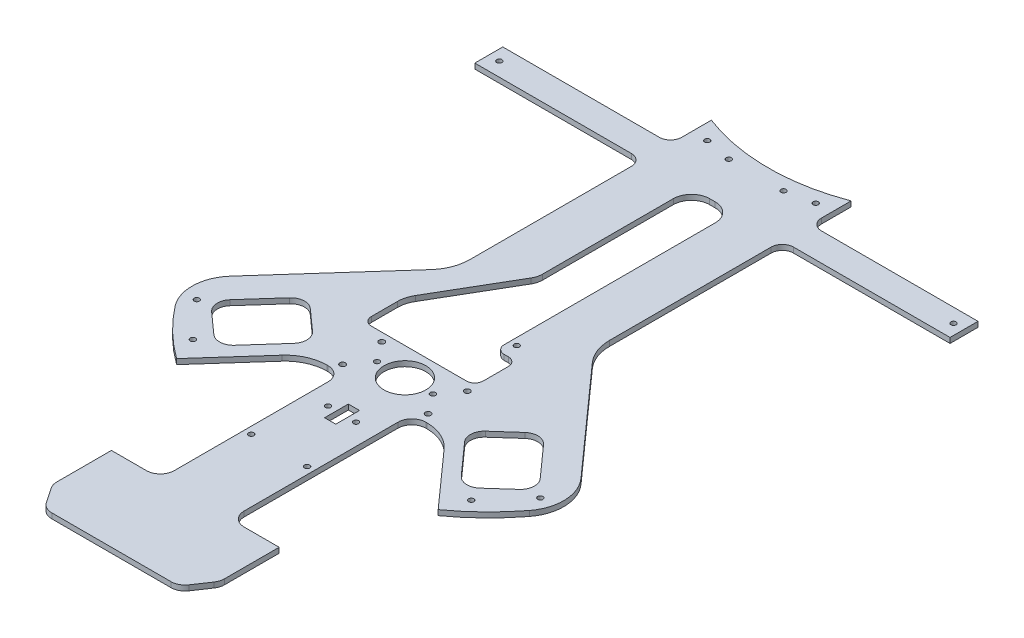
SolidWorks part; units mm, degrees
material "6063-T1"
ref_plane "Front Plane" through (0, 0, 0) normal (0, 0, 1) x (1, 0, 0)
ref_plane "Top Plane" through (0, 0, 0) normal (0, 1, 0) x (1, 0, 0)
ref_plane "Right Plane" through (0, 0, 0) normal (1, 0, 0) x (0, 0, -1)
sketch "Sketch1" plane through (0, 0, 0) normal (0, 1, 0) x (1, 0, 0)
  line L0 (-63.5, 31.75) -> (-178.5164, -97.0677)
  line L1 (-215.9, 31.75) -> (215.9, 31.75)
  line L2 (-215.9, 31.75) -> (-215.9, -31.75)
  line L3 (-215.9, -31.75) -> (215.9, -31.75)
  line L4 (215.9, 31.75) -> (215.9, -31.75)
  line L5 (-215.9, 31.75) -> (215.9, -31.75) construction
  line L6 (-215.9, -31.75) -> (215.9, 31.75) construction
  line L7 (63.5, 31.75) -> (-63.5, 31.75)
  line L8 (63.5, 31.75) -> (63.5, 292.608)
  line L9 (63.5, 292.608) -> (-63.5, 292.608)
  line L10 (-63.5, 31.75) -> (-63.5, 292.608)
  line L11 (0, -31.75) -> (-118.8264, -164.8348)
  line L12 (0, -31.75) -> (118.8264, -164.8348)
  line L13 (63.5, 31.75) -> (178.5164, -97.0677)
  line L14 (-62.3664, -101.6) -> (62.3664, -101.6)
  circle A1 centre (0, 0) radius 25.4 construction
  circle A2 centre (-25.4, 0) radius 2.3813
  circle A3 centre (25.4, 0) radius 2.3812
  circle A4 centre (0, 0) radius 203.2
  circle A5 centre (0, -76.2) radius 25.4 construction
  circle A6 centre (-25.4, -76.2) radius 2.3813
  circle A7 centre (25.4, -76.2) radius 2.3813
  point P0 (0, 0)
  dimension "D5" = 4.7625
  dimension "D6" = 4.7625
  dimension "D7" = 101.6
  dimension "D8" = 50.8
  dimension "D10" = 406.4
  dimension "D14" = 4.7625
  dimension "D15" = 4.7625
  dimension "D16" = 50.8
  dimension "D1" = 431.8
  dimension "D2" = 63.5
  dimension "D3" = 127
  dimension "D4" = 63.5
  dimension "D9" = 260.858
  dimension "D11" = 59.69
  dimension "D12" = 59.69
  dimension "D13" = 76.2
extrude "Boss-Extrude1" add sketch "Sketch1" along normal blind 4.7625 contours L10 L1 L8 L9 | L4 L1 L2 L3 A3 A2 | L0 A4 L11 L3 | L12 A4 L13 L3 | A4 L8 L9 L10 | L11 L14 L12 region at (0, 0, 3.2765) region at (0, 0, -115.8234) region at (-100.5416, 0, 84.5084) region at (0, 0, -246.176) region at (0, 0, 78.3341) region at (100.5416, 0, 84.5084)
sketch "Sketch2" plane through (0, 4.7625, 0) normal (0, 1, 0) x (1, 0, 0)
  line L0 (0, 292.608) -> (0, -101.6) construction
  line L1 (63.5, 292.608) -> (-63.5, 292.608) construction
  line L2 (-62.3664, -101.6) -> (62.3664, -101.6) construction
  circle A0 centre (25.4, 279.908) radius 2.3813
  circle A1 centre (50.8, 279.908) radius 2.3813
  circle A2 centre (-50.8, 279.908) radius 2.3813
  circle A3 centre (-25.4, 279.908) radius 2.3813
  dimension "D3" = 4.7625
  dimension "D4" = 4.7625
  dimension "D1" = 25.4
  dimension "D2" = 50.8
  dimension "D5" = 12.7
  dimension "D6" = 12.7
extrude "Cut-Extrude1" cut sketch "Sketch2" against normal through all
fillet "Fillet1" radius 38.1 4 edges at (63.5, 2.3813, -31.75) (-63.5, 2.3813, -31.75) (62.3664, 2.3813, 101.6) (-62.3664, 2.3813, 101.6)
sketch "Sketch4" plane through (0, 4.7625, 0) normal (0, 1, 0) x (1, 0, 0)
  line L0 (0, 292.608) -> (0, 0) construction
  line L1 (63.5, 292.608) -> (-63.5, 292.608) construction
  line L2 (0, 0) -> (0, -190.5) construction
  line L3 (0, 0) -> (-156.0485, -109.2663) construction
  circle A0 centre (0, 0) radius 190.5 construction
  circle A1 centre (-156.0485, -109.2663) radius 2.3813
  circle A2 centre (-126.4791, -142.4545) radius 2.3813
  circle A3 centre (126.4791, -142.4545) radius 2.3813
  circle A4 centre (156.0485, -109.2663) radius 2.3813
  dimension "D1" = 381
  dimension "D4" = 4.7625
  dimension "D5" = 4.7625
  dimension "D2" = 44.45
  dimension "D3" = 55
extrude "Cut-Extrude3" cut sketch "Sketch4" against normal through all
fillet "Fillet2" radius 38.1 2 edges at (178.5164, 2.3813, 97.0677) (-178.5164, 2.3813, 97.0677)
sketch "Sketch5" plane through (0, 4.7625, 0) normal (0, 1, 0) x (1, 0, 0)
  line L0 (-149.2765, -103.5959) -> (-111.3829, -137.4296)
  line L1 (-149.2765, -103.5959) -> (-106.9843, -56.229)
  line L2 (-111.3829, -137.4296) -> (-69.0908, -90.0627)
  line L3 (-106.9843, -56.229) -> (-69.0908, -90.0627)
  line L8 (-73.7278, -114.3247) -> (-118.8264, -164.8348) construction
  line L9 (0, 292.608) -> (0, -101.6) construction
  line L10 (63.5, 292.608) -> (-63.5, 292.608) construction
  line L11 (106.9843, -56.229) -> (69.0908, -90.0627)
  line L12 (111.3829, -137.4296) -> (69.0908, -90.0627)
  line L13 (149.2765, -103.5959) -> (106.9843, -56.229)
  line L14 (149.2765, -103.5959) -> (111.3829, -137.4296)
  line L15 (-45.3077, -101.6) -> (45.3077, -101.6) construction
  dimension "D1" = 50.8
  dimension "D2" = 12.7
  dimension "D3" = 63.5
  dimension "D4" = 25.4
extrude "Cut-Extrude4" cut sketch "Sketch5" against normal through all
fillet "Fillet3" radius 12.7 8 edges at (111.3829, 2.3813, 137.4296) (69.0908, 2.3813, 90.0627) (106.9843, 2.3813, 56.229) (149.2765, 2.3813, 103.5959) (-69.0908, 2.3813, 90.0627) (-106.9843, 2.3813, 56.229) (-149.2765, 2.3813, 103.5959) (-111.3829, 2.3813, 137.4296)
sketch "Sketch6" plane through (0, 4.7625, 0) normal (0, 1, 0) x (1, 0, 0)
  circle A0 centre (0, -76.2) radius 19.05
  dimension "D1" = 38.1
  dimension "D2" = 76.2
extrude "Cut-Extrude5" cut sketch "Sketch6" against normal through all
sketch "Sketch7" plane through (0, 4.7625, 0) normal (0, 1, 0) x (1, 0, 0)
  line L0 (-45.3077, -101.6) -> (45.3077, -101.6) construction
  line L1 (-19.05, 203.2) -> (19.05, 203.2)
  line L2 (-19.05, 203.2) -> (-19.05, -50.8)
  line L3 (-19.05, -50.8) -> (19.05, -50.8)
  line L4 (19.05, 203.2) -> (19.05, -50.8)
  line L5 (-19.05, 203.2) -> (19.05, -50.8) construction
  line L6 (-19.05, -50.8) -> (19.05, 203.2) construction
  point P0 (0, 76.2)
  dimension "D1" = 38.1
  dimension "D2" = 50.8
  dimension "D3" = 254
extrude "Cut-Extrude6" cut sketch "Sketch7" against normal through all
sketch "Sketch8" plane through (0, 4.7625, 0) normal (0, 1, 0) x (1, 0, 0)
  line L0 (-19.05, -50.8) -> (19.05, -50.8) construction
  line L1 (-63.5, -50.8) -> (38.1, -50.8)
  line L2 (-63.5, -50.8) -> (-63.5, -12.7)
  line L3 (-63.5, -12.7) -> (38.1, -12.7)
  line L4 (38.1, -50.8) -> (38.1, -12.7)
  dimension "D1" = 101.6
  dimension "D2" = 38.1
  dimension "D3" = 38.1
extrude "Cut-Extrude7" cut sketch "Sketch8" against normal through all
sketch "Sketch9" plane through (0, 4.7625, 0) normal (0, 1, 0) x (1, 0, 0)
  line L0 (-63.5, -12.7) -> (-19.05, 63.5)
  line L1 (-19.05, 203.2) -> (-19.05, -12.7) construction
  line L2 (-19.05, 63.5) -> (-19.05, -12.7)
  line L3 (-19.05, -12.7) -> (-63.5, -12.7)
  dimension "D1" = 76.2
extrude "Cut-Extrude8" cut sketch "Sketch9" against normal through all
fillet "Fillet4" radius 25.4 1 edges at (-63.5, 2.3813, 12.7)
fillet "Fillet5" radius 7.62 4 edges at (-63.5, 2.3813, 50.8) (38.1, 2.3813, 50.8) (38.1, 2.3813, 12.7) (19.05, 2.3813, 12.7)
fillet "Fillet8" radius 16.51 3 edges at (-19.05, 2.3813, -203.2) (19.05, 2.3813, -203.2) (-19.05, 2.3813, -63.5)
sketch "Sketch10" plane through (0, 4.7625, 0) normal (0, 1, 0) x (1, 0, 0)
  line L0 (0, 431.8) -> (0, 0) construction
  line L1 (0, 431.8) -> (-24.8652, 242.9298) construction
  line L2 (0, 431.8) -> (-49.305, 247.7911) construction
  circle A0 centre (0, 431.8) radius 177.8
  circle A1 centre (0, 431.8) radius 190.5 construction
  circle A2 centre (-49.305, 247.7911) radius 2.3812
  circle A3 centre (-24.8652, 242.9298) radius 2.3813
  circle A6 centre (24.8652, 242.9298) radius 2.3813
  circle A7 centre (49.305, 247.7911) radius 2.3812
  dimension "D1" = 355.6
  dimension "D3" = 381
  dimension "D4" = 4.7625
  dimension "D5" = 4.7625
  dimension "D6" = 7.5
  dimension "D7" = 15
  dimension "D2" = 431.8
extrude "Cut-Extrude9" cut sketch "Sketch10" against normal through all
sketch "Sketch11" plane through (0, 4.7625, 0) normal (0, 1, 0) x (1, 0, 0)
  line L1 (-215.9, 228.6) -> (215.9, 228.6)
  line L2 (-215.9, 228.6) -> (-215.9, 203.2)
  line L3 (-215.9, 203.2) -> (215.9, 203.2)
  line L4 (215.9, 228.6) -> (215.9, 203.2)
  line L5 (-215.9, 228.6) -> (215.9, 203.2) construction
  line L6 (-215.9, 203.2) -> (215.9, 228.6) construction
  point P0 (0, 215.9)
  dimension "D1" = 431.8
  dimension "D2" = 25.4
  dimension "D3" = 203.2
extrude "Boss-Extrude2" add sketch "Sketch11" against normal blind 4.7625
fillet "Fillet9" radius 10.16 4 edges at (63.5, 2.3813, -203.2) (63.5, 2.3813, -228.6) (-63.5, 2.3813, -203.2) (-63.5, 2.3813, -228.6)
sketch "Sketch12" plane through (0, 4.7625, 0) normal (0, 1, 0) x (1, 0, 0)
  line L0 (73.66, 203.2) -> (215.9, 203.2) construction
  line L1 (215.9, 203.2) -> (215.9, 228.6) construction
  line L2 (-215.9, 203.2) -> (-73.66, 203.2) construction
  line L3 (-215.9, 228.6) -> (-215.9, 203.2) construction
  circle A0 centre (-206.375, 215.9) radius 2.3813
  circle A1 centre (206.375, 215.9) radius 2.3813
  dimension "D1" = 4.7625
  dimension "D2" = 4.7625
  dimension "D3" = 12.7
  dimension "D4" = 9.525
  dimension "D5" = 12.7
  dimension "D6" = 9.525
extrude "Cut-Extrude10" cut sketch "Sketch12" against normal through all
sketch "Sketch13" plane through (0, 4.7625, 0) normal (0, 1, 0) x (1, 0, 0)
  line L0 (-45.3077, -101.6) -> (45.3077, -101.6) construction
  line L1 (-31.75, -101.6) -> (31.75, -101.6)
  line L2 (-31.75, -101.6) -> (-31.75, -266.7)
  line L3 (-31.75, -266.7) -> (31.75, -266.7)
  line L4 (31.75, -101.6) -> (31.75, -266.7)
  dimension "D1" = 63.5
  dimension "D2" = 31.75
  dimension "D3" = 165.1
extrude "Boss-Extrude3" add sketch "Sketch13" against normal up to surface (4.7625 mm away) up to face at (-206.375, 0, -213.5187)
fillet "Fillet10" radius 12.7 2 edges at (31.75, 2.3813, 101.6) (-31.75, 2.3813, 101.6)
sketch "Sketch14" plane through (0, 4.7625, 0) normal (0, 1, 0) x (1, 0, 0)
  circle A0 centre (-25.4, -190.5) radius 2.3813
  circle A1 centre (25.4, -190.5) radius 2.3813
  circle A2 centre (-25.4, -76.2) radius 2.3813 construction
  point P6 (0, 0)
  dimension "D1" = 4.7625
  dimension "D2" = 4.7625
  dimension "D3" = 114.3
  dimension "D4" = 25.4
  dimension "D5" = 25.4
extrude "Cut-Extrude11" cut sketch "Sketch14" against normal through all
sketch "Sketch15" plane through (0, 4.7625, 0) normal (0, 1, 0) x (1, 0, 0)
  line L0 (-31.75, -266.7) -> (31.75, -266.7) construction
  line L1 (-76.2, -266.7) -> (76.2, -266.7)
  line L2 (-76.2, -266.7) -> (-76.2, -342.9)
  line L3 (-76.2, -342.9) -> (76.2, -342.9)
  line L4 (76.2, -266.7) -> (76.2, -342.9)
  line L5 (-76.2, -266.7) -> (76.2, -342.9) construction
  line L6 (-76.2, -342.9) -> (76.2, -266.7) construction
  point P0 (0, -304.8)
  point P7 (0, 0)
  dimension "D1" = 76.2
  dimension "D2" = 152.4
extrude "Boss-Extrude4" add sketch "Sketch15" against normal up to surface (4.7625 mm away) up to face at (-25.4, 0, 192.8812)
fillet "Fillet11" radius 12.7 2 edges at (31.75, 2.3813, 266.7) (-31.75, 2.3813, 266.7)
sketch "Sketch16" plane through (0, 4.7625, 0) normal (0, 1, 0) x (1, 0, 0)
  line L1 (-5.08, -122.555) -> (5.08, -122.555)
  line L2 (-5.08, -122.555) -> (-5.08, -144.145)
  line L3 (-5.08, -144.145) -> (5.08, -144.145)
  line L4 (5.08, -122.555) -> (5.08, -144.145)
  line L5 (-5.08, -122.555) -> (5.08, -144.145) construction
  line L6 (-5.08, -144.145) -> (5.08, -122.555) construction
  point P0 (0, -133.35)
  dimension "D1" = 10.16
  dimension "D2" = 21.59
  dimension "D3" = 133.35
extrude "Cut-Extrude12" cut sketch "Sketch16" against normal through all
sketch "Sketch17" plane through (0, 4.7625, 0) normal (0, 1, 0) x (1, 0, 0)
  line L0 (-5.08, -144.145) -> (5.08, -144.145) construction
  line L2 (-5.08, -133.35) -> (5.08, -133.35) construction
  line L3 (-5.08, -122.555) -> (-5.08, -144.145) construction
  line L4 (5.08, -144.145) -> (5.08, -122.555) construction
  circle A0 centre (-12.7, -133.35) radius 2.3812
  circle A1 centre (12.7, -133.35) radius 2.3812
  point P6 (0, -144.145)
  point P7 (0, 0)
  point P8 (-12.7, -135.1558)
  point P11 (0, 0)
  dimension "D1" = 4.7625
  dimension "D2" = 4.7625
  dimension "D3" = 25.4
  dimension "D4" = 12.7
extrude "Cut-Extrude13" cut sketch "Sketch17" against normal through all
chamfer "Chamfer1" distance 15.24 angle 56 1 edges at (-76.2, 2.3813, 342.9) first distance on face at (0, 2.3813, 342.9)
chamfer "Chamfer2" distance 15.24 angle 56 1 edges at (76.2, 2.3813, 342.9) first distance on face at (7.62, 2.3813, 342.9)
fillet "Fillet13" radius 12.7 4 edges at (76.2, 2.3813, 320.3058) (60.96, 2.3813, 342.9) (-60.96, 2.3813, 342.9) (-76.2, 2.3813, 320.3058)
sketch "Sketch18" plane through (0, 4.7625, 0) normal (0, 1, 0) x (1, 0, 0)
  line L0 (0, -57.15) -> (0, -144.145) construction
  line L1 (-5.08, -144.145) -> (5.08, -144.145) construction
  line L2 (-27.7812, -76.2) -> (27.7812, -76.2) construction
  circle A0 centre (38.862, -93.98) radius 2.54
  circle A1 centre (0, -76.2) radius 19.05 construction
  circle A2 centre (25.4, -76.2) radius 2.3813 construction
  circle A3 centre (-38.862, -93.98) radius 2.54
  circle A4 centre (-25.4, -76.2) radius 2.3813 construction
  circle A5 centre (38.862, -58.42) radius 2.54
  circle A6 centre (-38.862, -58.42) radius 2.54
  dimension "D3" = 5.08
  dimension "D1" = 17.78
  dimension "D2" = 38.862
extrude "Cut-Extrude14" cut sketch "Sketch18" against normal through all
